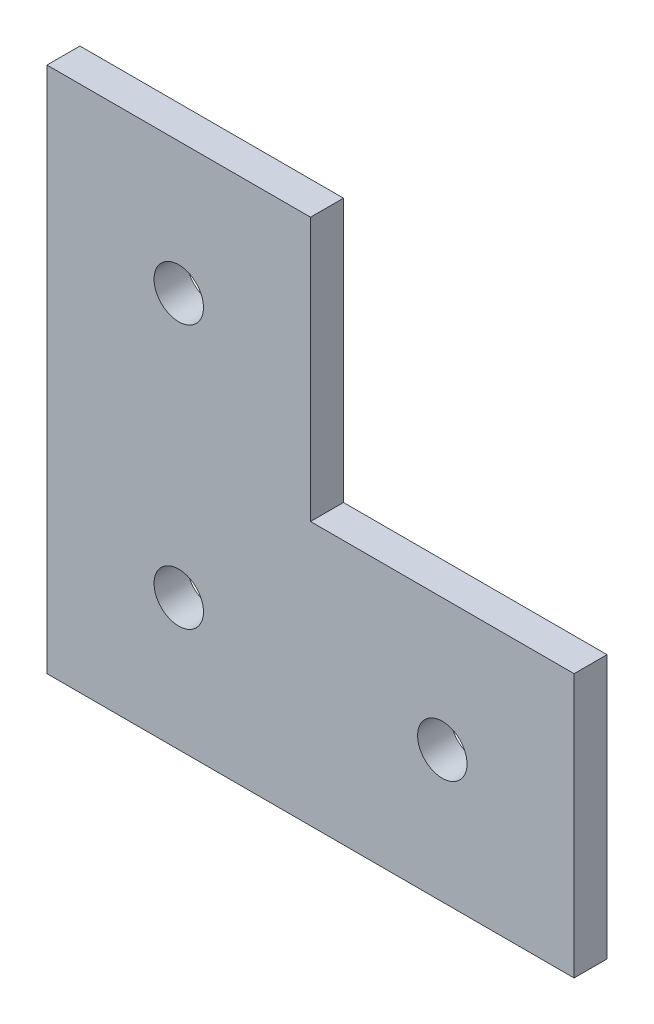
SolidWorks part; units mm, degrees
ref_plane "Front Plane" through (0, 0, 0) normal (0, 0, 1) x (1, 0, 0)
ref_plane "Top Plane" through (0, 0, 0) normal (0, 1, 0) x (1, 0, 0)
ref_plane "Right Plane" through (0, 0, 0) normal (1, 0, 0) x (0, 0, -1)
sketch "Sketch1" plane through (0, 0, 0) normal (0, 0, 1) x (1, 0, 0)
  line L1 (0, 0) -> (50.8, 0)
  line L2 (0, 0) -> (0, 50.8)
  line L3 (0, 50.8) -> (50.8, 50.8)
  line L4 (50.8, 0) -> (50.8, 50.8)
  line L5 (50.8, 50.8) -> (25.4, 50.8)
  line L6 (50.8, 50.8) -> (50.8, 25.4)
  line L7 (50.8, 25.4) -> (25.4, 25.4)
  line L8 (25.4, 50.8) -> (25.4, 25.4)
  circle A0 centre (12.7, 12.7) radius 2.3813
  circle A1 centre (38.1, 12.7) radius 2.3813
  circle A2 centre (38.1, 38.1) radius 2.3813
  circle A3 centre (12.7, 38.1) radius 2.3813
  dimension "D5" = 4.7625
  dimension "D1" = 50.8
  dimension "D2" = 50.8
  dimension "D3" = 25.4
  dimension "D4" = 25.4
  dimension "D6" = 12.7
  dimension "D7" = 12.7
  dimension "D8" = 2
  dimension "D9" = 2
extrude "Boss-Extrude1" add sketch "Sketch1" along normal blind 3.175 contours L8 L3 L2 L1 L4 L7 A3 A1 A0 region at (21.1667, 21.1667, 0)
